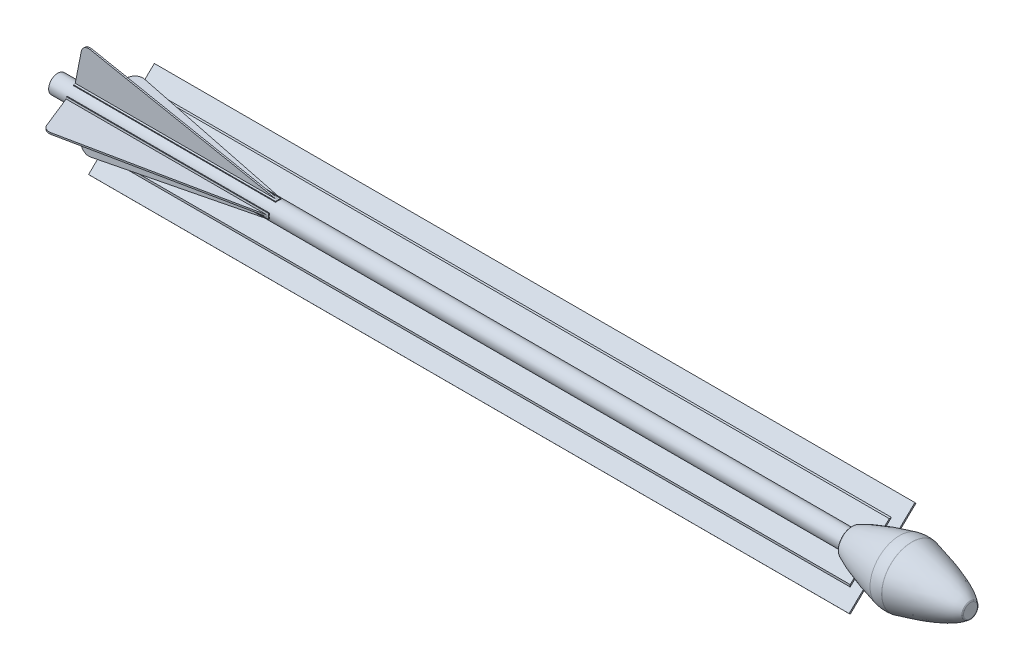
SolidWorks part; units mm, degrees
ref_plane "正面" through (0, 0, 0) normal (0, 0, 1) x (1, 0, 0)
ref_plane "平面" through (0, 0, 0) normal (0, 1, 0) x (1, 0, 0)
ref_plane "右側面" through (0, 0, 0) normal (1, 0, 0) x (0, 0, -1)
sketch "ｽｹｯﾁ1" plane through (0, 0, 0) normal (0, 0, 1) x (1, 0, 0)
  line L0 (-30.4177, 20.3227) -> (-30.4177, -19.1312)
  line L1 (-69.8771, 9.5958) -> (-69.8771, -8.4042)
  line L5 (8.174, 5.5958) -> (8.174, -4.4042)
  line L6 (-38.4177, 20.0342) -> (-38.4177, -18.8426)
  line L7 (10.8234, 0.5958) -> (-591.826, 0.5958)
  line L8 (-591.826, 6.5958) -> (-74.6461, 6.5958)
  line L9 (-591.826, 6.5958) -> (-591.826, -5.4042)
  line L10 (-591.826, -5.4042) -> (-74.6461, -5.4042)
  line L11 (-74.6461, 6.5958) -> (-74.6461, -5.4042)
  line L12 (-591.826, 6.5958) -> (-74.6461, -5.4042) construction
  line L13 (-591.826, -5.4042) -> (-74.6461, 6.5958) construction
  line L14 (-74.6461, -4.4042) -> (-591.826, -4.4042)
  line L15 (-74.6461, -4.4042) -> (-74.6461, 5.5958)
  line L16 (-74.6461, 5.5958) -> (-591.826, 5.5958)
  line L17 (-591.826, -4.4042) -> (-591.826, 5.5958)
  line L18 (-74.6461, -4.4042) -> (-591.826, 5.5958) construction
  line L19 (-74.6461, 5.5958) -> (-591.826, -4.4042) construction
  line L20 (-74.6461, 6.5958) -> (-56.932, 6.5958)
  line L21 (-74.6461, 6.5958) -> (-74.6461, -5.4042)
  line L22 (-74.6461, -5.4042) -> (-56.932, -5.4042)
  line L23 (-56.932, 6.5958) -> (-56.932, -5.4042)
  line L24 (-74.6461, 6.5958) -> (-56.932, -5.4042) construction
  line L25 (-74.6461, -5.4042) -> (-56.932, 6.5958) construction
  line L26 (-74.6461, 5.5958) -> (-56.932, 5.5958)
  line L27 (-74.6461, 5.5958) -> (-74.6461, -4.4042)
  line L28 (-74.6461, -4.4042) -> (-56.932, -4.4042)
  line L29 (-56.932, 5.5958) -> (-56.932, -4.4042)
  line L30 (-74.6461, 5.5958) -> (-56.932, -4.4042) construction
  line L31 (-74.6461, -4.4042) -> (-56.932, 5.5958) construction
  circle A0 centre (-33.7114, 0.5958) radius 20
  parabola Q1 (-38.4177, -18.8426) -> (-38.4177, 20.0342) focus (-76.1023, 0.5958) apex (-78.4613, 0.5958)
  parabola Q2 (-30.4177, -19.1312) -> (-30.4177, 20.3227) focus (8.4644, 0.5958) apex (10.8234, 0.5958)
  point P5 (-333.236, 0.5958)
  point P22 (-591.826, 0.5958)
  point P23 (-333.236, 0.5958)
  point P30 (-65.7891, 0.5958)
  point P33 (-65.7891, 0.5958)
  dimension "D1" = 40
  dimension "D18" = 40
  dimension "D7" = 20
  dimension "D9" = 0
  dimension "D10" = 0
  dimension "D11" = 20
  dimension "D13" = 20
  dimension "D15" = 20
  dimension "D2" = 18
  dimension "D5" = 10
  dimension "D8" = 2.359
  dimension "D19" = 78.0511
  dimension "D3" = 2.359
  dimension "D17" = 12
  dimension "D21" = 600
  dimension "D22" = 10
revolve "回転2" add sketch "ｽｹｯﾁ1" angle 360 about L7
fillet "ﾌｨﾚｯﾄ2" radius 1 2 edges at (-69.8771, 9.5958, 0) (8.174, 5.5958, 0)
sketch "ｽｹｯﾁ5" plane through (-591.826, 0, 0) normal (-1, 0, 0) x (0, 0, 1)
  circle A0 centre (0, 0.5958) radius 6.5
  circle A1 centre (0, 0.5958) radius 7.57
  dimension "D1" = 13
extrude "ﾎﾞｽ - 押し出し2" add sketch "ｽｹｯﾁ5" along normal blind 2 separate body
sketch "ｽｹｯﾁ6" plane through (0, 0, 0) normal (0, 0, 1) x (1, 0, 0)
  line L0 (-591.826, 6.5958) -> (-591.826, -5.4042) construction
  line L1 (-579.826, 2.2958) -> (-446.826, 2.2958)
  line L2 (-579.826, 2.2958) -> (-579.826, -1.1042)
  line L3 (-579.826, -1.1042) -> (-446.826, -1.1042)
  line L4 (-446.826, 2.2958) -> (-446.826, -1.1042)
  line L5 (-579.826, 2.2958) -> (-446.826, -1.1042) construction
  line L6 (-579.826, -1.1042) -> (-446.826, 2.2958) construction
  line L7 (-591.826, -5.4042) -> (-69.8771, -5.4042) construction
  point P4 (-513.326, 0.5958)
  point P7 (-579.826, 0.5958)
  dimension "D1" = 12
  dimension "D2" = 133
  dimension "D3" = 3.4
  dimension "D4" = 6
extrude "ﾎﾞｽ - 押し出し3" add sketch "ｽｹｯﾁ6" along normal up to surface and the other way up to surface up to face at (-593.826, -5.9042, 0) other way up to face at (-593.826, -5.9042, 0)
sketch "ｽｹｯﾁ7" plane through (0, 0, 0) normal (0, 1, 0) x (1, 0, 0)
  line L0 (-591.826, 6) -> (-591.826, -6) construction
  line L1 (-579.826, 1.7) -> (-446.826, 1.7)
  line L2 (-579.826, 1.7) -> (-579.826, -1.7)
  line L3 (-579.826, -1.7) -> (-446.826, -1.7)
  line L4 (-446.826, 1.7) -> (-446.826, -1.7)
  line L5 (-579.826, 1.7) -> (-446.826, -1.7) construction
  line L6 (-579.826, -1.7) -> (-446.826, 1.7) construction
  line L7 (-591.826, -6) -> (-579.826, -6) construction
  point P4 (-513.326, 0)
  point P7 (-579.826, 0)
  dimension "D1" = 3.4
  dimension "D2" = 133
  dimension "D3" = 12
  dimension "D4" = 6
extrude "ﾎﾞｽ - 押し出し4" add sketch "ｽｹｯﾁ7" along normal up to surface and the other way up to surface up to face at (-593.826, -5.9042, 0) other way up to face at (-593.826, -5.9042, 0)
sketch "ｽｹｯﾁ8" plane through (-593.826, 0, 0) normal (-1, 0, 0) x (0, 0, 1)
  circle A0 centre (0, 0.5958) radius 8.0163
  circle A1 centre (0, 0.5958) radius 5
  circle A2 centre (0, 0.5958) radius 6.5
extrude "ｶｯﾄ - 押し出し1" cut sketch "ｽｹｯﾁ8" against normal blind 182 and the other way blind 2 contours A1
sketch "ｽｹｯﾁ9" plane through (-591.826, 0, 0) normal (-1, 0, 0) x (0, 0, 1)
  line L5 (0, 0.5958) -> (7, 0.5958)
  line L6 (0, 0.5958) -> (0, -6.4042)
  line L7 (0, -6.4042) -> (7, -6.4042)
  line L8 (7, 0.5958) -> (7, -6.4042)
  line L9 (0, 0.5958) -> (7, -6.4042) construction
  line L10 (0, -6.4042) -> (7, 0.5958) construction
  line L11 (0, 0.5958) -> (10, 0.5958)
  line L12 (0, 0.5958) -> (0, -9.4042)
  line L13 (0, -9.4042) -> (10, -9.4042)
  line L14 (10, 0.5958) -> (10, -9.4042)
  line L15 (0, 0.5958) -> (10, -9.4042) construction
  line L16 (0, -9.4042) -> (10, 0.5958) construction
  point P4 (3.5, -2.9042)
  point P10 (5, -4.4042)
  dimension "D1" = 7
  dimension "D2" = 7
  dimension "D3" = 10
  dimension "D4" = 10
extrude "ﾎﾞｽ - 押し出し5" add sketch "ｽｹｯﾁ9" along normal blind 12 separate body contours L14 L11 L8 L7 L12 L13
sketch "ｽｹｯﾁ10" plane through (0, 0.5958, 0) normal (0, 1, 0) x (1, 0, 0)
  line L0 (-579.826, 1.7) -> (-579.826, -1.7) construction
  line L1 (-579.826, -31.5) -> (-447.826, -31.5)
  line L2 (-579.826, -31.5) -> (-579.826, -5.5)
  line L3 (-579.826, -5.5) -> (-447.826, -5.5)
  line L4 (-447.826, -31.5) -> (-447.826, -5.5)
  line L5 (-579.826, -31.5) -> (-447.826, -5.5) construction
  line L6 (-579.826, -5.5) -> (-447.826, -31.5) construction
  line L7 (-579.826, -6.5) -> (-446.826, -6.5) construction
  line L8 (-579.826, -6.5) -> (-569.826, -31.5)
  line L9 (-569.826, -31.5) -> (-447.826, -6.5)
  line L10 (-608.1921, 0) -> (-614.5212, 0) construction
  line L11 (-579.826, 5.5) -> (-447.826, 31.5) construction
  line L12 (-579.826, 31.5) -> (-447.826, 5.5) construction
  line L13 (-569.826, 31.5) -> (-447.826, 6.5)
  line L14 (-579.826, 6.5) -> (-569.826, 31.5)
  line L15 (-447.826, 31.5) -> (-447.826, 5.5)
  line L16 (-579.826, 5.5) -> (-447.826, 5.5)
  line L17 (-579.826, 31.5) -> (-579.826, 5.5)
  line L18 (-579.826, 31.5) -> (-447.826, 31.5)
  circle A0 centre (-566.7357, -25.7628) radius 5
  circle A1 centre (-566.7357, 25.7628) radius 5
  point P4 (-513.826, -18.5)
  point P26 (-513.826, 18.5)
  dimension "D5" = 10
  dimension "D1" = 26
  dimension "D2" = 0
  dimension "D3" = 1
  dimension "D4" = 132
  dimension "D6" = 10
extrude "ﾎﾞｽ - 押し出し6" add sketch "ｽｹｯﾁ10" along normal blind 0.5 and the other way blind 0.5 contours L13 A1 L14 L17 L16 L15 | A1 | A0 L9 L4 L3 L2 L8 | A0
sketch "ｽｹｯﾁ11" plane through (0, 0, 0) normal (0, 0, -1) x (-1, 0, 0)
  line L0 (579.826, 7.0958) -> (446.826, 7.0958) construction
  line L1 (579.826, 6.0958) -> (447.826, 6.0958)
  line L2 (579.826, 6.0958) -> (579.826, 32.0958)
  line L3 (579.826, 32.0958) -> (447.826, 32.0958)
  line L4 (447.826, 6.0958) -> (447.826, 32.0958)
  line L5 (579.826, 6.0958) -> (447.826, 32.0958) construction
  line L6 (579.826, 32.0958) -> (447.826, 6.0958) construction
  line L7 (579.826, 6.8695) -> (579.826, 6.3499) construction
  line L8 (579.826, 7.0958) -> (574.9079, 32.0958)
  line L9 (574.9079, 32.0958) -> (447.826, 7.0958)
  line L14 (603.826, 0.5958) -> (610.125, 0.5958) construction
  line L15 (579.826, -30.9042) -> (447.826, -4.9042) construction
  line L16 (579.826, -4.9042) -> (447.826, -30.9042) construction
  line L17 (574.9079, -30.9042) -> (447.826, -5.9042)
  line L18 (579.826, -5.9042) -> (574.9079, -30.9042)
  line L19 (447.826, -4.9042) -> (447.826, -30.9042)
  line L20 (579.826, -30.9042) -> (447.826, -30.9042)
  line L21 (579.826, -4.9042) -> (579.826, -30.9042)
  line L22 (579.826, -4.9042) -> (447.826, -4.9042)
  circle A0 centre (570.9671, 26.2247) radius 5
  circle A1 centre (570.9671, -25.0332) radius 5
  point P4 (513.826, 19.0958)
  point P26 (513.826, -17.9042)
  dimension "D7" = 10
  dimension "D1" = 26
  dimension "D2" = 1
  dimension "D3" = 132
  dimension "D4" = 0
  dimension "D5" = 0
  dimension "D6" = 0
extrude "ﾎﾞｽ - 押し出し7" add sketch "ｽｹｯﾁ11" along normal blind 0.5 and the other way blind 0.5 contours L17 A1 L18 L21 L22 L19 | A0 L9 L4 L1 L2 L8 | A0
sketch "ｽｹｯﾁ12" plane through (0, 0, 0) normal (0, 0, -1) x (-1, 0, 0)
  line L1 (591.826, -9.4042) -> (609.9524, -9.4042)
  line L2 (591.826, -9.4042) -> (591.826, 7.468)
  line L3 (591.826, 7.468) -> (609.9524, 7.468)
  line L4 (609.9524, -9.4042) -> (609.9524, 7.468)
  line L5 (591.826, -9.4042) -> (609.9524, 7.468) construction
  line L6 (591.826, 7.468) -> (609.9524, -9.4042) construction
  point P4 (600.8892, -0.9681)
extrude "ｶｯﾄ - 押し出し2" cut sketch "ｽｹｯﾁ12" against normal blind 30.5
fillet "ﾌｨﾚｯﾄ3" radius 1 1 edges at (-30.4177, 20.3227, 0)
ref_plane "平面1" through (-571.3781, 0, 0) normal (1, 0, 0) x (0, 0, -1)
sketch "ｽｹｯﾁ14" plane through (-571.3781, 0, 0) normal (1, 0, 0) x (0, 0, -1)
  line L0 (27.6198, 0.0958) -> (0.5, -25.9983)
  line L1 (27.6198, 0.0958) -> (26.1775, 0.0958)
  line L2 (26.1775, 0.0958) -> (0.5, -24.6105)
  line L3 (0.5, -24.6105) -> (0.5, -25.9983)
  line L4 (0.5, -41.5051) -> (43.7362, 0.0958)
  line L7 (0.5, -29.9391) -> (0.5, -5.9042) construction
  line L9 (30.6611, 0.0958) -> (6.5, 0.0958) construction
  line L10 (0.5, -41.5051) -> (-0.1933, -40.7845)
  line L11 (-0.1933, -40.7845) -> (43.0429, 0.8164)
  line L12 (43.0429, 0.8164) -> (43.7362, 0.0958)
  dimension "D1" = 1
  dimension "D2" = 0
  dimension "D3" = 0
  dimension "D4" = 60
  dimension "D5" = 1
extrude "ﾎﾞｽ - 押し出し8" add sketch "ｽｹｯﾁ14" along normal blind 500
equation "\"a\"=2.359"
equation "\"D8@ｽｹｯﾁ1\"=\"a\""
equation "\"D3@ｽｹｯﾁ1\"=\"a\""
